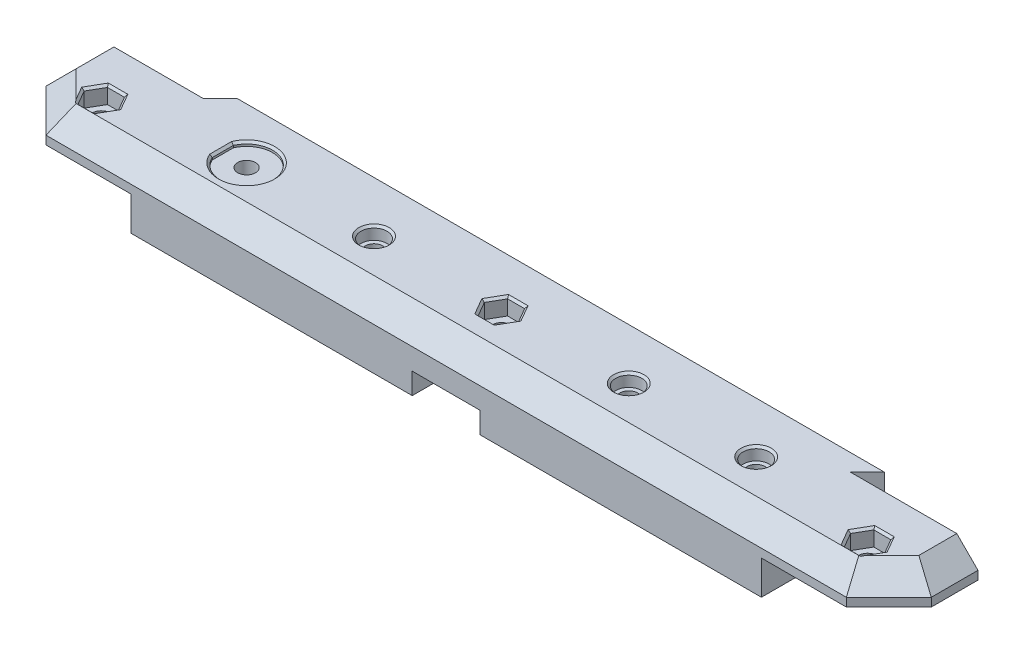
SolidWorks part; units mm, degrees
ref_plane "Front Plane" through (0, 0, 0) normal (0, 0, 1) x (1, 0, 0)
ref_plane "Top Plane" through (0, 0, 0) normal (0, 1, 0) x (1, 0, 0)
ref_plane "Right Plane" through (0, 0, 0) normal (1, 0, 0) x (0, 0, -1)
sketch "Sketch1" plane through (0, 0, 0) normal (0, 1, 0) x (1, 0, 0)
  line L0 (178.4924, 21) -> (208.4924, 21)
  line L1 (10, 0) -> (198.4924, 0)
  line L2 (0, 10) -> (0, 21)
  line L3 (0, 21) -> (30, 21)
  line L4 (208.4924, 10) -> (208.4924, 21)
  line L6 (30, 21) -> (30, 25)
  line L7 (30, 25) -> (178.4924, 25)
  line L8 (178.4924, 21) -> (178.4924, 25)
  line L9 (0, 10) -> (10, 0)
  line L10 (198.4924, 0) -> (208.4924, 10)
  line L11 (30, 25) -> (104.2462, -49.2462) construction
  line L12 (104.2462, -49.2462) -> (178.4924, 25) construction
  point P0 (0, 0)
  point P3 (208.4924, 0)
  dimension "D1" = 30
  dimension "D2" = 30
  dimension "D3" = 4
  dimension "D4" = 105
  dimension "D5" = 21
extrude "Main Base Extrude" add sketch "Sketch1" along normal blind 7
sketch "Sketch3" plane through (0, 0, 0) normal (0, 1, 0) x (1, 0, 0)
  line L0 (10, 0) -> (198.4924, 0) construction
  line L1 (30, 25) -> (178.4924, 25)
  line L2 (30, 25) -> (30, 0)
  line L3 (30, 0) -> (178.4924, 0)
  line L4 (178.4924, 25) -> (178.4924, 0)
extrude "Lower Base Extrude" add sketch "Sketch3" against normal blind 8
sketch "Sketch6" plane through (0, -8, 0) normal (0, -1, 0) x (1, 0, 0)
  line L0 (96.2462, 0) -> (112.2462, 0)
  line L1 (100.2462, -17) -> (108.2462, -17)
  line L2 (108.2462, -17) -> (112.2462, -10.0718)
  line L6 (96.2462, -10.0718) -> (100.2462, -17)
  line L7 (178.4924, -25) -> (30, -25) construction
  line L8 (30, 0) -> (178.4924, 0) construction
  line L9 (96.2462, -10.0718) -> (96.2462, 0)
  line L11 (112.2462, -10.0718) -> (112.2462, 0)
  line L14 (108.2462, -3.1436) -> (100.2462, -3.1436) [skipped]
  line L15 (100.2462, -3.1436) -> (96.2462, -10.0718) construction
  line L16 (112.2462, -10.0718) -> (108.2462, -3.1436) construction
  circle A0 centre (104.2462, -10.0718) radius 6.9282 construction
  point P13 (104.2462, 0)
  dimension "D1" = 8
  dimension "D2" = 8
  dimension "D3" = 16
extrude "Floor Tab Cut" cut sketch "Sketch6" against normal blind 5
chamfer "Main Body Chamfer" distance 5 angle 45 5 edges at (208.4924, 7, -15.5) (203.4924, 7, -5) (104.2462, 7, 0) (5, 7, -5) (0, 7, -15.5)
sketch "Sketch11" plane through (0, 7, 0) normal (0, 1, 0) x (1, 0, 0)
  line L0 (30, 21) -> (26, 25)
  line L1 (26, 25) -> (30, 25)
  line L2 (30, 25) -> (30, 21)
  line L3 (178.4924, 25) -> (182.4924, 21)
  line L4 (203.4924, 21) -> (178.4924, 21) construction
  line L5 (182.4924, 21) -> (178.4924, 21)
  line L6 (178.4924, 21) -> (178.4924, 25)
extrude "Column Chamfer-LF" [suppressed] add sketch "Sketch11" against normal up to surface (15 mm away)
sketch "Sketch12" plane through (0, 7, 0) normal (0, 1, 0) x (1, 0, 0)
  line L0 (30, 25) -> (26, 21)
  line L1 (30, 21) -> (5, 21) construction
  line L2 (26, 21) -> (30, 21)
  line L3 (30, 21) -> (30, 25)
  line L4 (178.4924, 21) -> (182.4924, 25)
  line L5 (182.4924, 25) -> (178.4924, 25)
  line L6 (178.4924, 25) -> (178.4924, 21)
extrude "Column Chamfer-RF" add sketch "Sketch12" against normal up to surface (15 mm away) up to face at (104.2462, -8, -10.4144)
sketch "Sketch17" [suppressed] plane through (0, -8, 0) normal (0, -1, 0) x (1, 0, 0)
  line L0 (178.4924, -25) -> (178.4924, -21)
  line L1 (178.4924, -21) -> (182.4924, -21)
  line L2 (182.4924, -21) -> (178.4924, -25)
extrude "Corner column Edge Trim - LF" [suppressed] cut sketch "Sketch17" against normal up to surface (8 mm away)
sketch "Sketch16" plane through (0, -8, 0) normal (0, -1, 0) x (1, 0, 0)
  line L0 (30, -25) -> (30, -21)
  line L1 (30, -21) -> (26, -21)
  line L2 (26, -21) -> (30, -25)
extrude "Corner Column Edge Trim - RF" cut sketch "Sketch16" against normal up to surface (8 mm away) up to face at (16, 0, -12.1667)
sketch "Sketch2" plane through (0, 7, 0) normal (0, 1, 0) x (1, 0, 0)
  line L0 (-1000, 9) -> (49000, 9) construction
  line L3 (30, 25) -> (30, 21) construction
  line L4 (178.4924, 21) -> (178.4924, 25) construction
  line L5 (182.4924, 25) -> (30, 25) construction
  circle A0 centre (14, 9) radius 2.1
  circle A1 centre (194.4924, 9) radius 2.1
  dimension "4.2" = 4.2
  dimension "D2" = 16
  dimension "D3" = 16
  dimension "D4" = 16
extrude "Column Connect Holes" cut sketch "Sketch2" against normal through all
sketch "Sketch4" plane through (0, 7, 0) normal (0, 1, 0) x (1, 0, 0)
  line L0 (104.2462, -975) -> (104.2462, 49025) construction
  line L1 (182.4924, 25) -> (30, 25) construction
  line L2 (0, 21) -> (104.2462, 125.2462) construction
  line L3 (104.2462, 125.2462) -> (208.4924, 21) construction
  circle A0 centre (74.2462, 13) radius 2.1
  circle A1 centre (44.2462, 13) radius 2.1
  circle A2 centre (164.2462, 13) radius 2.1
  circle A3 centre (134.2462, 13) radius 2.1
  dimension "D1" = 4.2
  dimension "D2" = 30
  dimension "D3" = 30
  dimension "D4" = 12
extrude "Wall Connect Holes" cut sketch "Sketch4" against normal through all
sketch "Sketch8" plane through (0, -3, 0) normal (0, -1, 0) x (1, 0, 0)
  line L4 (112.2462, 0) -> (96.2462, 0) construction
  line L5 (182.4924, -25) -> (30, -25) construction
  circle A0 centre (104.2462, -13) radius 2
  point P4 (104.2462, 0)
  dimension "D1" = 4
  dimension "D2" = 12
extrude "Floor Tab Hole Cut" cut sketch "Sketch8" against normal through all
sketch "Sketch5" plane through (0, -8, 0) normal (0, -1, 0) x (1, 0, 0)
  circle A19 centre (44.2462, -13) radius 4
  circle A21 centre (134.2462, -13) radius 4
  circle A22 centre (164.2462, -13) radius 4
  circle A23 centre (74.2462, -13) radius 4
  dimension "D1" = 8
extrude "Wall Connect Hole Countersink" cut sketch "Sketch5" against normal blind 5
sketch "Sketch9" plane through (0, 7, 0) normal (0, 1, 0) x (1, 0, 0)
  line L1 (16.0063, 12.475) -> (11.9937, 12.475)
  line L2 (11.9937, 12.475) -> (9.9874, 9)
  line L3 (9.9874, 9) -> (11.9937, 5.525)
  line L4 (11.9937, 5.525) -> (16.0063, 5.525)
  line L5 (16.0063, 5.525) -> (18.0126, 9)
  line L6 (18.0126, 9) -> (16.0063, 12.475)
  line L7 (106.2525, 16.475) -> (102.2399, 16.475)
  line L8 (102.2399, 16.475) -> (100.2336, 13)
  line L9 (100.2336, 13) -> (102.2399, 9.525)
  line L10 (102.2399, 9.525) -> (106.2525, 9.525)
  line L11 (106.2525, 9.525) -> (108.2588, 13)
  line L12 (108.2588, 13) -> (106.2525, 16.475)
  line L13 (196.4987, 12.475) -> (192.4861, 12.475)
  line L14 (192.4861, 12.475) -> (190.4798, 9)
  line L15 (190.4798, 9) -> (192.4861, 5.525)
  line L16 (192.4861, 5.525) -> (196.4987, 5.525)
  line L17 (196.4987, 5.525) -> (198.505, 9)
  line L18 (198.505, 9) -> (196.4987, 12.475)
  circle A0 centre (14, 9) radius 3.475 construction
  circle A1 centre (104.2462, 13) radius 3.475 construction
  circle A2 centre (194.4924, 9) radius 3.475 construction
  dimension "D1" = 6.95
extrude "Nut Insert Cut" cut sketch "Sketch9" against normal blind 4
chamfer "Connect Hole Countersink Chamfer" distance 0.5 angle 45 4 edges at (164.2462, -8, -17) (134.2462, -8, -17) (74.2462, -8, -17) (44.2462, -8, -17)
chamfer "Nut Insert Chamfer" distance 0.5 angle 45 18 edges at (191.483, 7, -10.7375) (191.483, 7, -7.2625) (194.4924, 7, -5.525) (197.5019, 7, -7.2625) (197.5019, 7, -10.7375) (194.4924, 7, -12.475) (101.2368, 7, -14.7375) (101.2368, 7, -11.2625) (104.2462, 7, -9.525) (107.2557, 7, -11.2625) (107.2557, 7, -14.7375) (104.2462, 7, -16.475) (10.9906, 7, -10.7375) (10.9906, 7, -7.2625) (14, 7, -5.525) (17.0094, 7, -7.2625) (17.0094, 7, -10.7375) (14, 7, -12.475)
ref_plane "Mid Plane" through (104.2462, 0, 0) normal (1, 0, 0) x (0, 0, -1)
sketch "Sketch10" plane through (0, 7, 0) normal (0, 1, 0) x (1, 0, 0)
  line L0 (38.6462, 10.5189) -> (38.6462, 15.4811)
  arc A0 (38.6462, 10.5189) -> (38.6462, 15.4811) centre (44.2462, 13) ccw
  arc A3 (38.6462, 15.4811) -> (38.6462, 10.5189) centre (44.2462, 13) ccw construction
  dimension "D1" = 12.25
  dimension "D2" = 5.6
extrude "Door Peg Sink-RF" cut sketch "Sketch10" against normal blind 1
chamfer "Door Peg Chamfer - RF" distance 0.5 angle 45 2 edges at (38.6462, 7, -13) (50.3712, 7, -13)
sketch "Sketch13" [suppressed] plane through (0, 7, 0) normal (0, 1, 0) x (1, 0, 0)
  line L0 (169.8462, 10.5189) -> (169.8462, 15.4811)
  arc A0 (169.8462, 15.4811) -> (169.8462, 10.5189) centre (164.2462, 13) ccw
  arc A1 (169.8462, 10.5189) -> (169.8462, 15.4811) centre (164.2462, 13) ccw construction
  dimension "D1" = 12.25
  dimension "D2" = 5.6
extrude "Door Peg Sink - LF" [suppressed] cut sketch "Sketch13" against normal blind 1
chamfer "Door Peg Chamfer - LF" [suppressed] distance 0.5 angle 45
sketch "Sketch14" plane through (0, 7, 0) normal (0, 1, 0) x (1, 0, 0)
  circle A0 centre (134.2462, 13) radius 3.075
  circle A1 centre (74.2462, 13) radius 3.075
  circle A2 centre (164.2462, 13) radius 3.075
  dimension "D1" = 6.15
  dimension "D2" = 6.15
extrude "Magnet Hole Cut - RF" cut sketch "Sketch14" against normal blind 3
chamfer "Magnet Hole Chamfer - RF" distance 0.5 angle 45 3 edges at (74.2462, 7, -9.925) (134.2462, 7, -9.925) (164.2462, 7, -9.925)
sketch "Sketch18" [suppressed] plane through (0, 7, 0) normal (0, 1, 0) x (1, 0, 0)
  circle A0 centre (44.2462, 13) radius 3.075
  circle A1 centre (74.2462, 13) radius 3.075
  circle A2 centre (134.2462, 13) radius 3.075
  dimension "D1" = 6.15
extrude "Magnet Hole Cut - LF" [suppressed] cut sketch "Sketch18" against normal blind 3
chamfer "Magnet Hole Chamfer - LF" [suppressed] distance 0.5 angle 45
